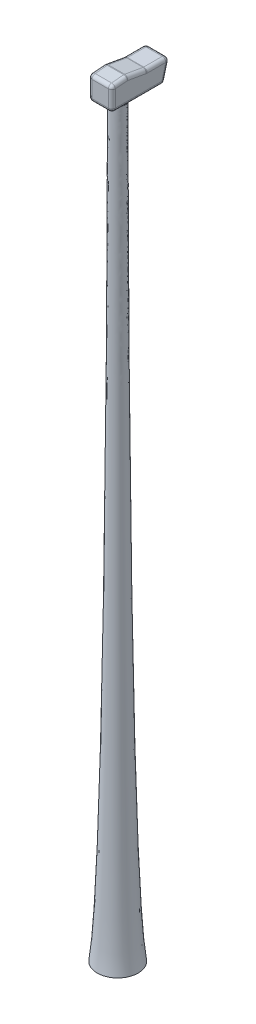
SolidWorks part; units mm, degrees
ref_plane "Ebene vorne" through (0, 0, 0) normal (0, 0, 1) x (1, 0, 0)
ref_plane "Ebene oben" through (0, 0, 0) normal (0, 1, 0) x (1, 0, 0)
ref_plane "Ebene rechts" through (0, 0, 0) normal (1, 0, 0) x (0, 0, -1)
sketch "Skizze2" plane through (0, 0, 0) normal (1, 0, 0) x (0, 0, -1)
  line L0 (500, -1000) -> (500, 1000)
  line L1 (-500, -500) -> (500, -500) construction
  line L2 (-500, -500) -> (-500, 500) construction
  line L3 (-500, 500) -> (500, 500) construction
  line L4 (500, -500) -> (500, 500) construction
  line L5 (-500, -500) -> (500, 500) construction
  line L6 (-500, 500) -> (500, -500) construction
  line L7 (500, 1000) -> (1850, 1118.1097)
  line L8 (1850, 1118.1097) -> (3500, 827.1702)
  line L9 (3500, 827.1702) -> (5500, 827.1702)
  line L10 (5500, 827.1702) -> (5010.4112, -1000)
  line L11 (5010.4112, -1000) -> (500, -1000)
  point P0 (0, 0)
  dimension "D1" = 1000
  dimension "D2" = 1000
  dimension "D3" = 5000
  dimension "D4" = 75
  dimension "D5" = 1350
  dimension "D6" = 1650
  dimension "D7" = 95
  dimension "D8" = 165
  dimension "D9" = 500
  dimension "D10" = 500
extrude "Aufsatz-Linear austragen1" add sketch "Skizze2" along normal blind 1000 and the other way blind 1000 contours L8 L9 L10 L11 L0 L7
fillet "Verrundung1" radius 300 18 edges at (-1000, 827.1702, -4500) (0, 827.1702, -5500) (1000, 827.1702, -4500) (-1000, 972.6399, -2675) (0, 827.1702, -3500) (1000, 972.6399, -2675) (-1000, 1059.0548, -1175) (0, 1118.1097, -1850) (1000, 1059.0548, -1175) (0, 1000, -500) (0, -1000, -500) (-1000, 0, -500) (-1000, -1000, -2755.2056) (-1000, -86.4149, -5255.2056) (0, -1000, -5010.4112) (1000, -86.4149, -5255.2056) (1000, -1000, -2755.2056) (1000, 0, -500)
sketch "Skizze3" plane through (0, 0, 0) normal (1, 0, 0) x (0, 0, -1)
  line L0 (800, -700) -> (4780.2131, -700) construction
  line L1 (1300, -700) -> (2000, -700)
  line L2 (1300, -700) -> (1300, -1200)
  line L5 (-816.0524, 0) -> (6168.6291, 0) construction
  line L6 (2000, 0) -> (2000, -65000) construction
  line L7 (500, -700) -> (500, 725.1006) construction
  line L9 (2000, -65000) -> (250, -65000)
  line L10 (2000, -700) -> (2000, -65000)
  line L11 (1350, -1200) -> (1350, -1000)
  line L12 (4780.2131, -1000) -> (800, -1000) construction
  line L13 (1350, -1000) -> (1375, -1000)
  line L14 (1375, -1000) -> (1375, -1200)
  line L15 (1350, -1200) -> (1300, -1200)
  line L16 (962.3284, -1200) -> (1375, -1200) construction
  spline S0 degree 3 poles (1375, -1200) (1375, -2032.5048) (1337.2877, -57815.76) (250, -65000) knots 0 0 0 0 1 1 1 1
  point P22 (2000, -707.7272)
  dimension "D1" = 1500
  dimension "D2" = 1750
  dimension "D3" = 65000
  dimension "D4" = 875
  dimension "D5" = 39000
  dimension "D6" = 500
  dimension "D7" = 700
  dimension "D8" = 50
  dimension "D9" = 25
revolve "Rotation1" add sketch "Skizze3" angle 360 about L6
equation "\"hubDiameter\"=1"
